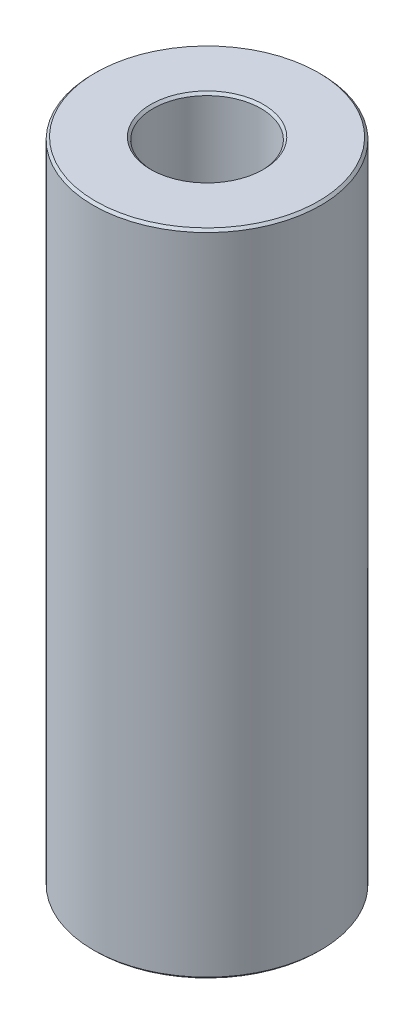
SolidWorks part; units mm, degrees
ref_plane "Front Plane" through (0, 0, 0) normal (0, 0, 1) x (1, 0, 0)
ref_plane "Top Plane" through (0, 0, 0) normal (0, 1, 0) x (1, 0, 0)
ref_plane "Right Plane" through (0, 0, 0) normal (1, 0, 0) x (0, 0, -1)
sketch "Sketch1" plane through (0, 0, 0) normal (0, 1, 0) x (1, 0, 0)
  circle A0 centre (0, 0) radius 50
  dimension "SLEEVE_OD" = 100
extrude "Boss-Extrude1" add sketch "Sketch1" along normal blind 285.4375
sketch "Sketch2" plane through (0, 0, 0) normal (0, 1, 0) x (1, 0, 0)
  circle A0 centre (0, 0) radius 23.737
  dimension "BORE_D" = 47.4741
extrude "Cut-Extrude1" cut sketch "Sketch2" along normal through all
chamfer "Chamfer1" distance 1.0423 angle 45 4 edges at (0, 285.4375, 23.737) (0, 0, 23.737) (0, 0, 50) (0, 285.4375, 50)
